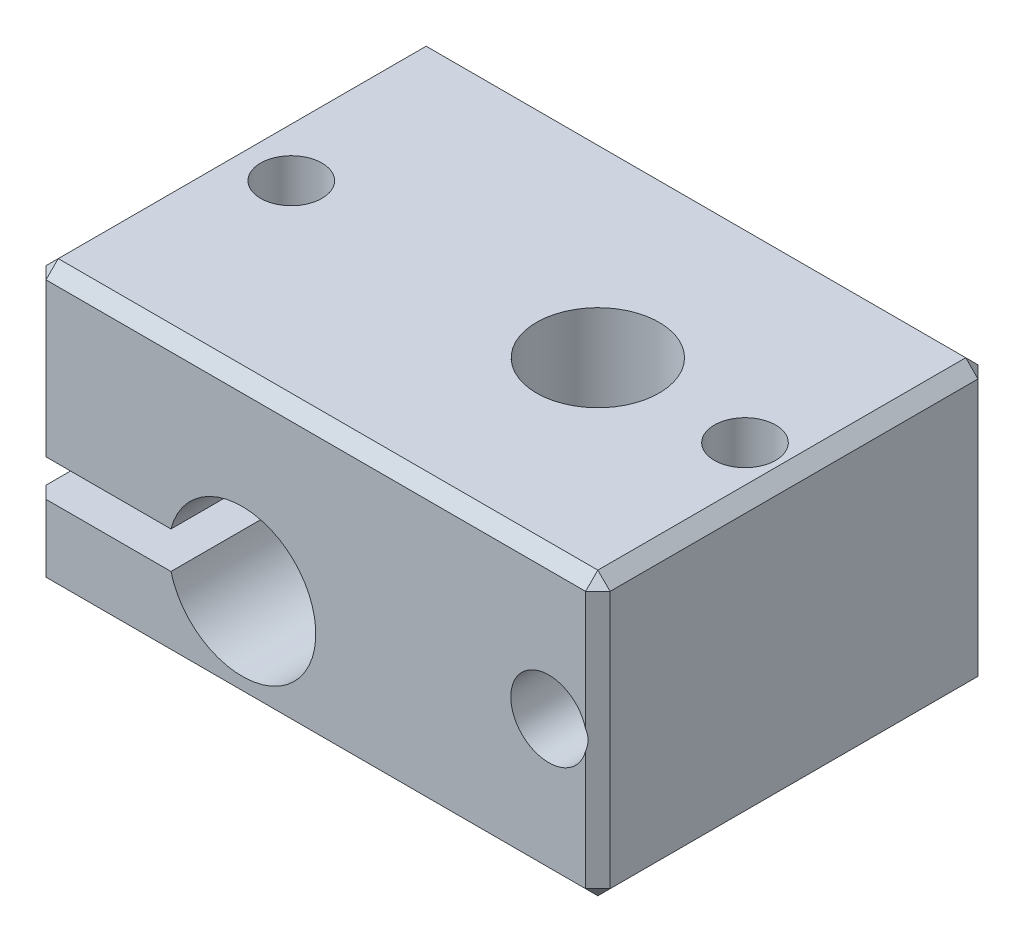
SolidWorks part; units mm, degrees
material "6061 Alloy"
ref_plane "Front Plane" through (0, 0, 0) normal (0, 0, 1) x (1, 0, 0)
ref_plane "Top Plane" through (0, 0, 0) normal (0, 1, 0) x (1, 0, 0)
ref_plane "Right Plane" through (0, 0, 0) normal (1, 0, 0) x (0, 0, -1)
sketch "Sketch1" plane through (0, 0, 0) normal (0, 1, 0) x (1, 0, 0)
  line L1 (0, 0) -> (23, 0)
  line L2 (0, 0) -> (0, 16)
  line L3 (0, 16) -> (23, 16)
  line L4 (23, 0) -> (23, 16)
  dimension "D1" = 16
  dimension "D2" = 23
extrude "Boss-Extrude1" add sketch "Sketch1" along normal blind 11.5
sketch "Sketch10" plane through (0, 0, 0) normal (0, 0, 1) x (1, 0, 0)
  line L0 (0, 0) -> (23, 0) construction
  line L1 (23, 11.5) -> (23, 0) construction
  circle A0 centre (21, 5.75) radius 1.55
  dimension "D1" = 3.1
  dimension "D2" = 5.75
  dimension "D3" = 2
extrude "Cut-Extrude2" cut sketch "Sketch10" against normal through all
hole_wizard "M3x0.5 Tapped Hole1" positions "Sketch7" profile "Sketch6" tap size "M3x0.5" standard "ANSI Metric" end condition up to next
sketch "Sketch7" plane through (0, 11.5, 0) normal (0, 1, 0) x (1, 0, 0)
  line L0 (0, 0) -> (23, 0) construction
  line L1 (23, 0) -> (23, 16) construction
  point P0 (2.5, 8)
  point P12 (21, 8)
  dimension "D1" = 8
  dimension "D2" = 20.5
  dimension "D3" = 2
cosmetic thread "Hole Thread2" parameters "D2"=3
sketch "Sketch6" plane through (2.5, 11.5, -8) normal (1, 0, 0) x (0, 0, 1)
  line L0 (0, 0) -> (0, 11.5)
  line L1 (0, 11.5) -> (1.25, 11.5)
  line L2 (1.25, 11.5) -> (1.25, 0)
  line L5 (1.25, 0) -> (0, 0)
  line L11 (0, -6.35) -> (0, 107.95) construction
  dimension "Thru Tap Drill Dia." = 2.5
  dimension "Thru Tap Drill Depth" = 11.5
cosmetic thread "Hole Thread4" parameters "D2"=3
hole_wizard "M6 Tapped Hole1" positions "Sketch5" profile "Sketch4" tap size "M6" standard "ISO" end condition through all
sketch "Sketch5" plane through (0, 11.5, 0) normal (0, 1, 0) x (1, 0, 0)
  line L0 (23, 0) -> (23, 16) construction
  line L1 (0, 0) -> (23, 0) construction
  point P0 (15, 8)
  dimension "D1" = 8
  dimension "D2" = 8
cosmetic thread "Hole Thread1" parameters "D2"=6
sketch "Sketch4" plane through (15, 11.5, -8) normal (1, 0, 0) x (0, 0, 1)
  line L0 (0, 0) -> (0, 11.5)
  line L1 (0, 11.5) -> (2.5, 11.5)
  line L2 (2.5, 11.5) -> (2.5, 0)
  line L5 (2.5, 0) -> (0, 0)
  line L11 (0, -6.35) -> (0, 107.95) construction
  dimension "Thru Tap Drill Dia." = 5
  dimension "Thru Tap Drill Depth" = 11.5
sketch "Sketch2" plane through (0, 0, 0) normal (0, 0, 1) x (1, 0, 0)
  line L0 (0, 0) -> (23, 0) construction
  line L1 (23, 11.5) -> (23, 0) construction
  line L2 (0, 11.5) -> (0, 0) construction
  line L3 (0, 4.75) -> (5.5953, 4.75)
  line L4 (0, 4.75) -> (0, 3.25)
  line L5 (0, 3.25) -> (5.5953, 3.25)
  line L6 (5.5953, 4.75) -> (5.5953, 3.25)
  line L7 (2.7976, 3.25) -> (2.7976, 4.75) construction
  line L8 (0, 4) -> (5.5953, 4) construction
  circle A0 centre (8.5, 4) radius 3
  point P86 (2.7976, 4)
  line M4 (0, 11.5) -> (0, 0)
  dimension "D2" = 14.5
  dimension "D3" = 6
  dimension "D1" = 4
  dimension "D4" = 1.5
extrude "Cut-Extrude1" cut sketch "Sketch2" against normal blind 16 contours A0 L3 L5 M4 | L6 A0 | L6 A0
hole_wizard "M3x0.5 Tapped Hole2" [suppressed] positions "Sketch9" profile "Sketch8" tap size "M3x0.5" standard "ANSI Metric"
sketch "Sketch9" plane through (0, 0, 0) normal (0, 0, 1) x (1, 0, 0)
  line L0 (0, 0) -> (20, 0) construction
  line L1 (20, 11.5) -> (20, 0) construction
  point P0 (16.5, 4.8)
  dimension "D1" = 4.8
  dimension "D2" = 3.5
sketch "Sketch8" plane through (16.5, 4.8, 0) normal (1, 0, 0) x (0, -1, 0)
  line L0 (0, 0) -> (0, 4.1511)
  line L1 (0, 4.1511) -> (1.25, 3.4)
  line L2 (1.25, 3.4) -> (1.25, 0)
  line L5 (1.25, 0) -> (0, 0)
  line L10 (0, 4.1511) -> (-1.25, 3.4) construction
  line L11 (0, -6.35) -> (0, 107.95) construction
  dimension "Tap Drill Dia." = 2.5
  dimension "Tap Drill Depth" = 3.4
  dimension "Drill Angle" = 118
cosmetic thread "Hole Thread3" [suppressed] parameters "D1"=3.4, "D2"=3
chamfer "Chamfer1" distance 0.5 angle 45 14 edges at (0, 1.625, -16) (0, 8.125, -16) (0, 0, -8) (23, 11.5, -8) (11.5, 0, -16) (23, 5.75, -16) (23, 0, -8) (0, 1.625, 0) (11.5, 0, 0) (23, 5.75, 0) (0, 8.125, 0) (11.5, 11.5, 0) (0, 11.5, -8) (11.5, 11.5, -16)
